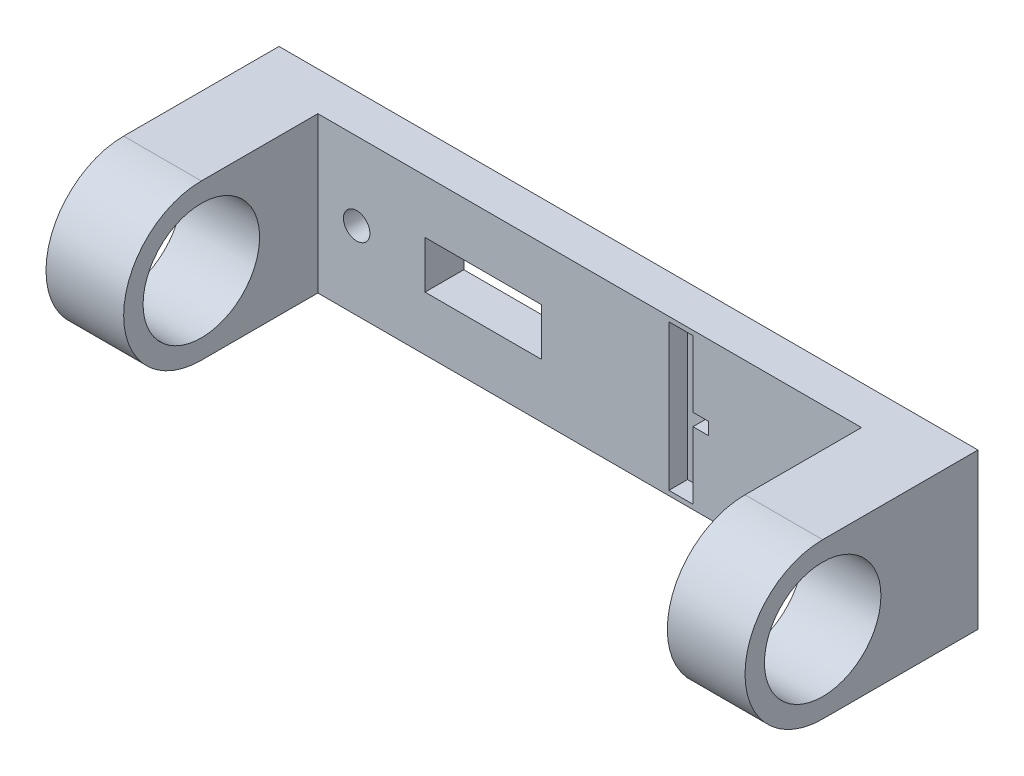
SolidWorks part; units mm, degrees
ref_plane "Plan de face" through (0, 0, 0) normal (0, 0, 1) x (1, 0, 0)
ref_plane "Plan de dessus" through (0, 0, 0) normal (0, 1, 0) x (1, 0, 0)
ref_plane "Plan de droite" through (0, 0, 0) normal (1, 0, 0) x (0, 0, -1)
sketch "Esquisse1" plane through (0, 0, 0) normal (0, 0, 1) x (1, 0, 0)
  line L1 (0, 0) -> (90, 0)
  line L2 (0, 0) -> (0, 20)
  line L3 (0, 20) -> (90, 20)
  line L4 (90, 0) -> (90, 20)
  dimension "D1" = 90
  dimension "D2" = 20
extrude "Boss.-Extru.1" add sketch "Esquisse1" along normal blind 5
sketch "Esquisse2" plane through (0, 0, 5) normal (0, 0, 1) x (1, 0, 0)
  line L0 (90, 20) -> (0, 20) construction
  line L1 (0, 0) -> (10, 0)
  line L2 (0, 0) -> (0, 20)
  line L3 (0, 20) -> (10, 20)
  line L4 (10, 0) -> (10, 20)
  dimension "D1" = 10
extrude "Boss.-Extru.2" add sketch "Esquisse2" along normal blind 30
sketch "Esquisse3" plane through (0, 0, 0) normal (-1, 0, 0) x (0, 0, 1)
  line L0 (0, 20) -> (0, 0) construction
  line L1 (35, 20) -> (0, 20) construction
  line L2 (35, 20) -> (35, 0) construction
  line L3 (35, 0) -> (0, 0) construction
  line L4 (35, 20) -> (20, 20)
  line L5 (35, 20) -> (35, 0)
  line L6 (35, 0) -> (20, 0)
  circle A0 centre (20, 10) radius 7.5
  arc A1 (20, 0) -> (20, 20) centre (20, 10) ccw
  dimension "D2" = 15
  dimension "D4" = 20
  dimension "D1" = 20
  dimension "D3" = 10
extrude "Enlèv. mat.-Extru.1" cut sketch "Esquisse3" against normal up to surface (10 mm away) up to face at (10, 10, 20)
ref_plane "Plan1" through (45, 0, 0) normal (1, 0, 0) x (0, 0, -1)
mirror "Symétrie1" about plane through (45, 0, 0) normal (1, 0, 0) of "Enlèv. mat.-Extru.1", "Boss.-Extru.2"
sketch "Esquisse5" plane through (0, 0, 5) normal (0, 0, 1) x (1, 0, 0)
  line L0 (80, 20) -> (10, 20) construction
  line L1 (55.2, 19.4) -> (58.3, 19.4)
  line L2 (55.2, 19.4) -> (55.2, 0.6)
  line L3 (55.2, 0.6) -> (58.3, 0.6)
  line L4 (58.3, 19.4) -> (58.3, 10.85)
  line L5 (80, 0) -> (80, 20) construction
  line L6 (58.3, 10.85) -> (60.3, 10.85)
  line L7 (60.3, 10.85) -> (60.3, 9.25)
  line L8 (60.3, 9.25) -> (58.3, 9.25)
  line L9 (58.3, 9.25) -> (58.3, 0.6)
  dimension "D1" = 18.8
  dimension "D2" = 3.1
  dimension "D3" = 0.6
  dimension "D4" = 21.7
  dimension "D5" = 8.65
  dimension "D6" = 1.6
  dimension "D7" = 2
extrude "Enlèv. mat.-Extru.2" cut sketch "Esquisse5" against normal offset from surface (2.4 mm away) 2.6 up to face at (45, 10, 0)
sketch "Esquisse6" plane through (0, 0, 5) normal (0, 0, 1) x (1, 0, 0)
  line L0 (80, 20) -> (10, 20) construction
  line L1 (10, 0) -> (10, 20) construction
  line L2 (80, 20) -> (80, 0) construction
  circle A0 centre (25, 10) radius 1.5 construction
  circle A1 centre (68, 10) radius 1.5
  dimension "D1" = 3
  dimension "D4" = 3
  dimension "D2" = 10
  dimension "D3" = 15
  dimension "D5" = 10
  dimension "D6" = 12
extrude "Enlèv. mat.-Extru.3" [suppressed] cut sketch "Esquisse6" against normal up to surface (5 mm away) up to face at (45, 10, 0)
sketch "Esquisse10" plane through (0, 0, 5) normal (0, 0, 1) x (1, 0, 0)
  line L0 (55.2, 19.4) -> (55.2, 0.6) construction
  line L1 (23.8, 13.1) -> (38.8, 13.1)
  line L2 (23.8, 13.1) -> (23.8, 7)
  line L3 (23.8, 7) -> (38.8, 7)
  line L4 (38.8, 13.1) -> (38.8, 7)
  line L5 (60.3, 10.05) -> (75.5405, 10.05) construction
  line L6 (60.3, 9.25) -> (60.3, 10.85) construction
  point P10 (23.8, 10.05)
  dimension "D1" = 16.4
  dimension "D2" = 15
  dimension "D3" = 6.1
extrude "Enlèv. mat.-Extru.4" cut sketch "Esquisse10" against normal up to surface (5 mm away) up to face at (45, 10, 0)
sketch "Esquisse11" plane through (0, 0, 5) normal (0, 0, 1) x (1, 0, 0)
  line L0 (0, 10) -> (91.8744, 10) construction
  line L1 (90, 0) -> (90, 20) construction
  line L4 (0, 20) -> (0, 0)
  line L5 (90, 20) -> (0, 20)
  line L6 (90, 0) -> (90, 20)
  line L7 (0, 0) -> (90, 0)
  line L8 (0, 20) -> (0, 0) construction
  line L9 (90, 20) -> (0, 20) construction
  line L10 (90, 0) -> (90, 20) construction
  line L11 (0, 0) -> (90, 0) construction
  circle A0 centre (15, 10) radius 1
  circle A1 centre (75, 10) radius 1
  dimension "D2" = 2
  dimension "D3" = 2
  dimension "D4" = 15
  dimension "D5" = 15
  dimension "D1" = 0
extrude "Enlèv. mat.-Extru.5" cut sketch "Esquisse11" against normal blind 10
hole_wizard "Dégagement M31" positions "Esquisse12" profile "Esquisse13" hole size "M3" standard "ISO" end condition through all
sketch "Esquisse12" plane through (0, 0, 5) normal (0, 0, 1) x (1, 0, 0)
  point P0 (15, 10)
  point P3 (75, 10)
sketch "Esquisse13" plane through (15, 10, 5) normal (1, 0, 0) x (0, -1, 0)
  line L0 (0, 0) -> (0, 5)
  line L1 (0, 5) -> (1.7, 5)
  line L2 (1.7, 5) -> (1.7, 0)
  line L5 (1.7, 0) -> (0, 0)
  line L11 (0, -6.35) -> (0, 107.95) construction
  dimension "Diamètre du perçage jusqu'au prochain" = 3.4
  dimension "Profondeur du perçage jusqu'au prochain" = 5
equation "\"D3@Esquisse5\"=(20-\"D1@Esquisse5\")/2"
